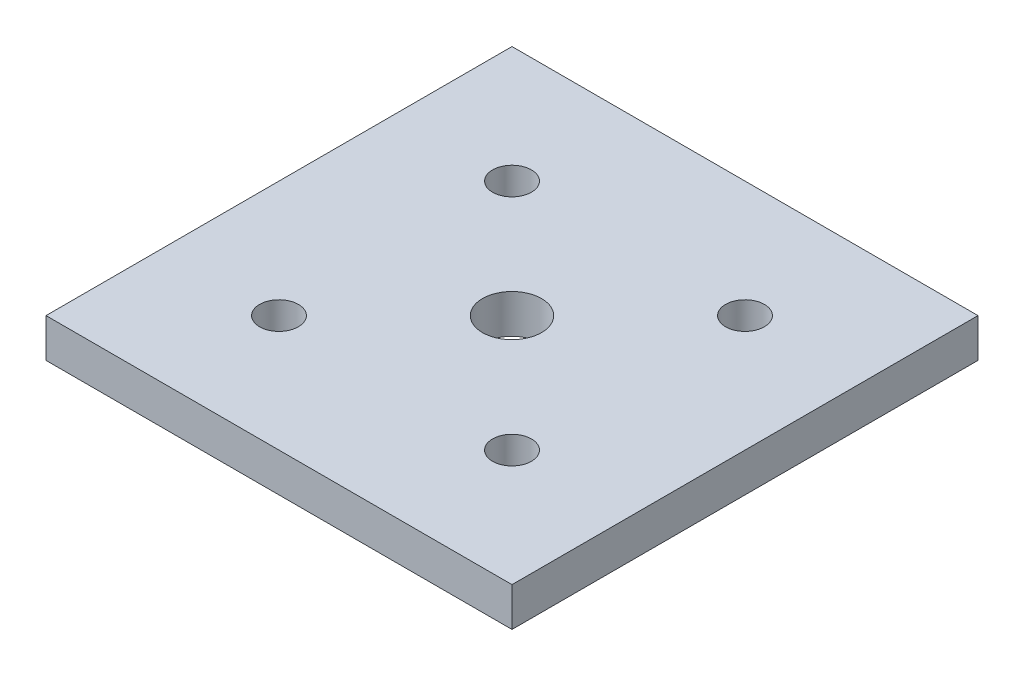
SolidWorks part; units mm, degrees
ref_plane "Front Plane" through (0, 0, 0) normal (0, 0, 1) x (1, 0, 0)
ref_plane "Top Plane" through (0, 0, 0) normal (0, 1, 0) x (1, 0, 0)
ref_plane "Right Plane" through (0, 0, 0) normal (1, 0, 0) x (0, 0, -1)
sketch "Sketch1" plane through (0, 0, 0) normal (0, 1, 0) x (1, 0, 0)
  line L0 (0, 28.2361) -> (0, -28.5398) construction
  line L1 (30, -30) -> (-30, -30)
  line L2 (30, -30) -> (30, 30)
  line L3 (30, 30) -> (-30, 30)
  line L4 (-30, -30) -> (-30, 30)
  line L5 (30, -30) -> (-30, 30) construction
  line L6 (30, 30) -> (-30, -30) construction
  line L7 (-35.2631, 0) -> (39.3471, 0) construction
  circle A0 centre (0, 0) radius 3.8
  circle A1 centre (-15, 15) radius 2.5
  circle A2 centre (15, 15) radius 2.5
  circle A3 centre (15, -15) radius 2.5
  circle A4 centre (-15, -15) radius 2.5
  point P0 (0, 0)
  point P14 (-30, 15)
  point P15 (-15, 30)
  dimension "D3" = 7.6
  dimension "D4" = 5
  dimension "D1" = 60
  dimension "D2" = 60
  dimension "D5" = 15
  dimension "D6" = 15
extrude "Boss-Extrude1" add sketch "Sketch1" along normal blind 5
